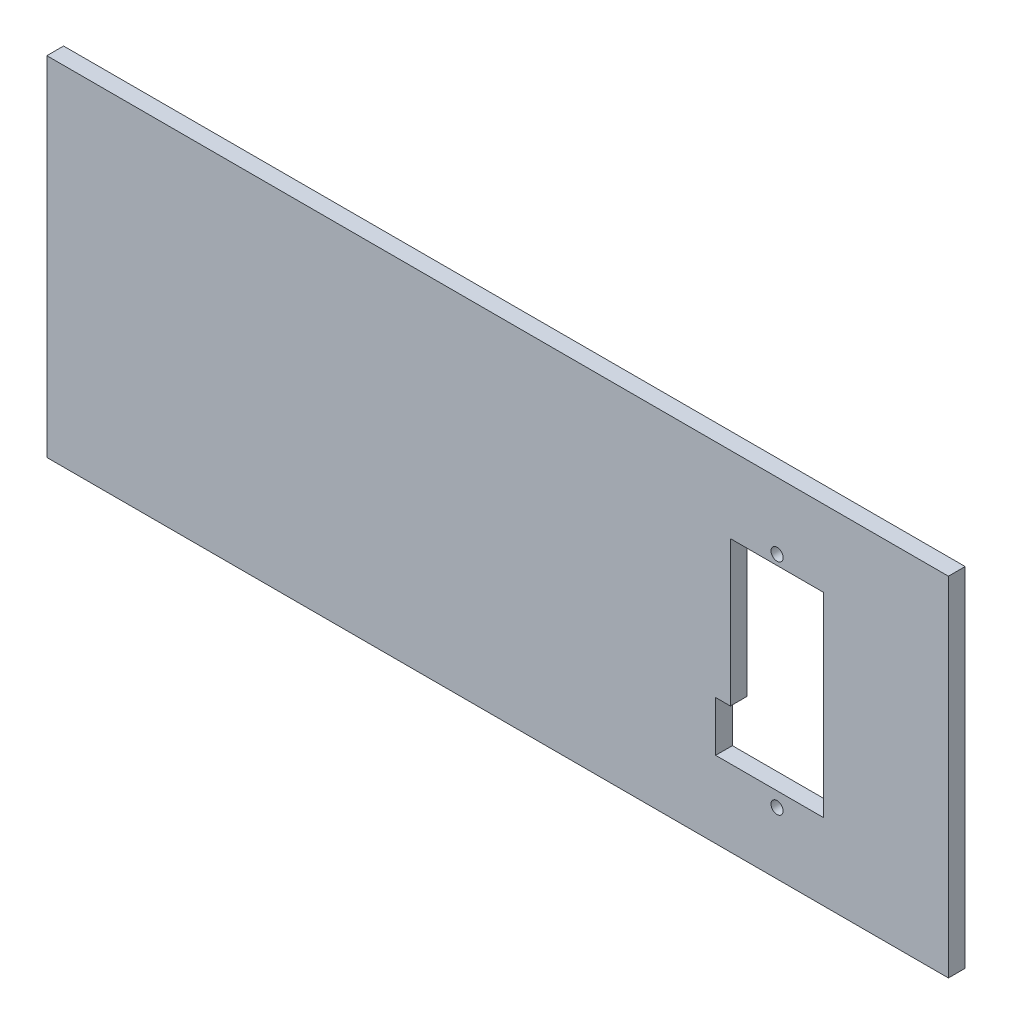
SolidWorks part; units mm, degrees
ref_plane "Front Plane" through (0, 0, 0) normal (0, 0, 1) x (1, 0, 0)
ref_plane "Top Plane" through (0, 0, 0) normal (0, 1, 0) x (1, 0, 0)
ref_plane "Right Plane" through (0, 0, 0) normal (1, 0, 0) x (0, 0, -1)
sketch "Sketch1" plane through (0, 0, 0) normal (0, 0, 1) x (1, 0, 0)
  line L1 (0, 0) -> (342, 0)
  line L2 (0, 0) -> (0, 132)
  line L3 (0, 132) -> (342, 132)
  line L4 (342, 0) -> (342, 132)
  line L9 (294.7, 29) -> (253.7, 29)
  line L10 (294.7, 29) -> (294.7, 103)
  line L11 (294.7, 103) -> (259.3, 103)
  line L12 (259.3, 103) -> (259.3, 48)
  line L13 (259.3, 48) -> (253.7, 48)
  line L14 (253.7, 48) -> (253.7, 29)
  line L15 (342, 66) -> (0, 66) construction
  line L16 (277, 103) -> (277, 106.7) construction
  line L17 (277, 23.5) -> (277, 103) construction
  circle A0 centre (277, 106.7) radius 2.3
  circle A1 centre (277, 23.5) radius 2.3
  point P13 (294.7, 66)
  point P14 (277, 103)
  dimension "D9" = 4.6
  dimension "D10" = 4.6
  dimension "D1" = 132
  dimension "D2" = 342
  dimension "D3" = 19
  dimension "D4" = 74
  dimension "D5" = 41
  dimension "D6" = 35.4
  dimension "D7" = 65
  dimension "D8" = 3.7
  dimension "D11" = 83.2
extrude "Boss-Extrude1" add sketch "Sketch1" along normal blind 6.35
